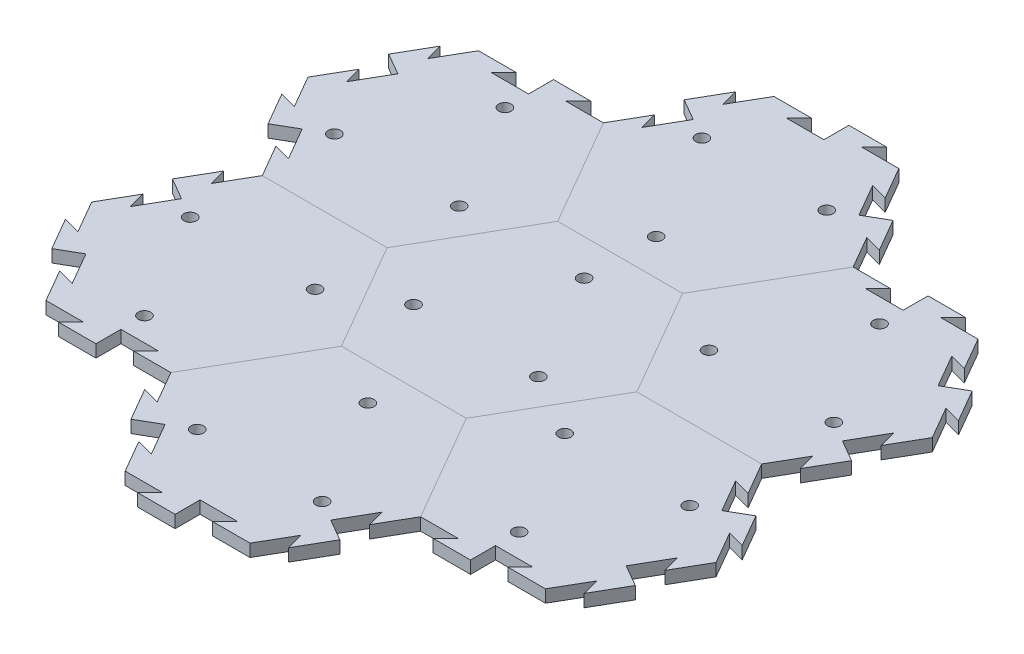
SolidWorks part; units mm, degrees
material "Cedar"
ref_plane "Front Plane" through (0, 0, 0) normal (0, 0, 1) x (1, 0, 0)
ref_plane "Top Plane" through (0, 0, 0) normal (0, 1, 0) x (1, 0, 0)
ref_plane "Right Plane" through (0, 0, 0) normal (1, 0, 0) x (0, 0, -1)
sketch "Sketch1" plane through (0, 0, 0) normal (0, 1, 0) x (1, 0, 0)
  line L0 (0, 0) -> (63.5, 0) construction
  line L1 (63.5, 0) -> (31.75, 54.9926)
  line L2 (31.75, 54.9926) -> (-31.75, 54.9926)
  line L3 (-31.75, 54.9926) -> (-63.5, 0)
  line L4 (-63.5, 0) -> (-31.75, -54.9926)
  line L5 (-31.75, -54.9926) -> (31.75, -54.9926)
  line L6 (31.75, -54.9926) -> (63.5, 0)
  circle A0 centre (0, 0) radius 54.9926 construction
  dimension "D1" = 63.5
extrude "Boss-Extrude1" add sketch "Sketch1" against normal blind 6.35
sketch "Sketch2" plane through (0, 0, 0) normal (0, 1, 0) x (1, 0, 0)
  point P1 (0, 0)
ref_axis "Axis1" through (0, 0, 0) along (0, 1, 0)
sketch "Sketch9" plane through (0, 0, 0) normal (0, 1, 0) x (1, 0, 0)
  line L1 (31.75, -18.3309) -> (0, 36.6617) construction
  line L2 (0, 36.6617) -> (-31.75, -18.3309) construction
  line L3 (-31.75, -18.3309) -> (31.75, -18.3309) construction
  circle A0 centre (0, 0) radius 18.3309 construction
  circle A1 centre (-31.75, -18.3309) radius 3.175
  dimension "D2" = 6.35
  dimension "D1" = 63.5
extrude "Cut-Extrude3" cut sketch "Sketch9" against normal through all
pattern_circular "CirPattern6" count 3 over 360 about axis through (0, 0, 0) along (0, 1, 0) of "Cut-Extrude3"
mirror "Mirror1" about plane through (31.75, -6.35, 54.9926) normal (0.866, 0, 0.5) of bodies 121 101
sketch "Sketch5" plane through (0, 0, 0) normal (0, 1, 0) x (1, 0, 0)
  line L0 (127, 0) -> (136.525, -16.4978) construction
  line L1 (127, 0) -> (158.75, -54.9926) construction
  line L2 (136.525, -16.4978) -> (127.8507, -14.1735)
  line L3 (127.8507, -14.1735) -> (137.3757, -30.6713)
  line L4 (137.3757, -30.6713) -> (142.875, -27.4963)
  line L5 (127, 0) -> (158.75, -54.9926) construction
  line L6 (136.525, -16.4978) -> (142.875, -27.4963)
  dimension "D1" = 45
  dimension "D2" = 6.35
sketch "Sketch6" plane through (0, 0, 0) normal (0, 1, 0) x (1, 0, 0)
  line L0 (31.75, -54.9926) -> (158.75, -54.9926) construction
  point P4 (95.25, -54.9926)
ref_axis "Axis3" through (95.25, 0, 54.9926) along (0, 1, 0)
extrude "Cut-Extrude2" cut sketch "Sketch5" against normal through all
sketch "Sketch7" plane through (0, 0, 0) normal (0, 1, 0) x (1, 0, 0)
  line L0 (142.875, -27.4963) -> (158.75, -54.9926) construction
  line L1 (142.875, -27.4963) -> (158.75, -54.9926) construction
  line L2 (142.875, -27.4963) -> (148.3743, -24.3213)
  line L3 (148.3743, -24.3213) -> (157.8993, -40.8191)
  line L4 (157.8993, -40.8191) -> (149.225, -38.4948)
  line L5 (149.225, -38.4948) -> (142.875, -27.4963)
  line L6 (149.225, -38.4948) -> (158.75, -54.9926) construction
  line L7 (149.225, -38.4948) -> (158.75, -54.9926) construction
  dimension "D1" = 45
  dimension "D2" = 6.35
extrude "Boss-Extrude3" add sketch "Sketch7" against normal up to surface (6.35 mm away) up to face at (63.5, -6.35, 33.4867)
pattern_circular "CirPattern3" count 3 every 60 about axis through (95.25, 0, 54.9926) along (0, 1, 0) of "Cut-Extrude2", "Boss-Extrude3" reverse direction yes
pattern_circular "CirPattern5" count 6 over 360 about axis through (0, 0, 0) along (0, 1, 0) of bodies 113
